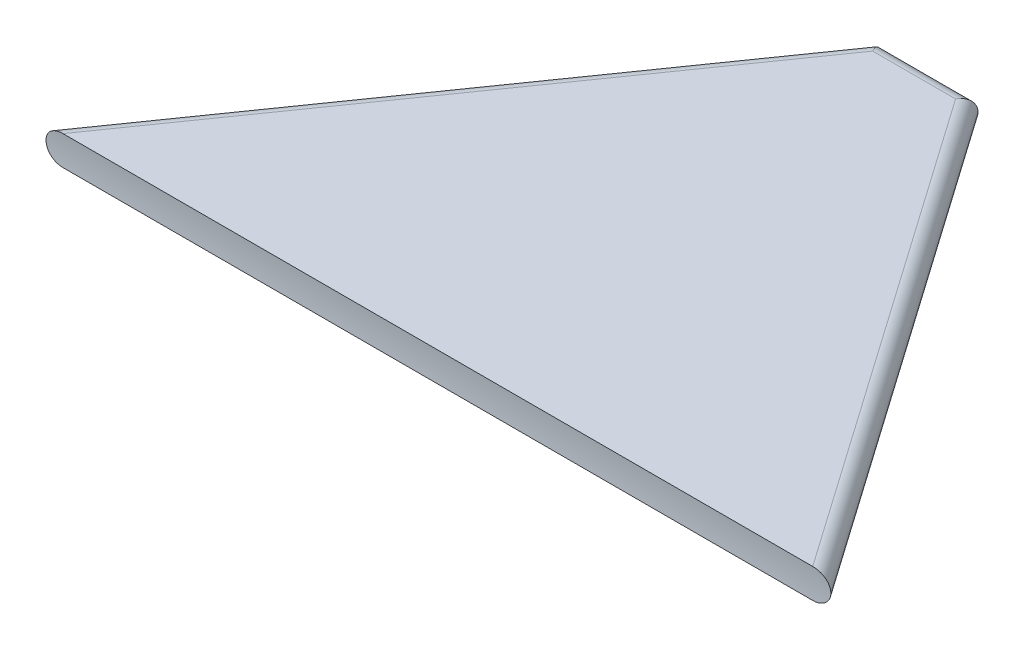
SolidWorks part; units mm, degrees
ref_plane "Спереди" through (0, 0, 0) normal (0, 0, 1) x (1, 0, 0)
ref_plane "Сверху" through (0, 0, 0) normal (0, 1, 0) x (1, 0, 0)
ref_plane "Справа" through (0, 0, 0) normal (1, 0, 0) x (0, 0, -1)
sketch "Эскиз1" plane through (0, 0, 0) normal (0, 1, 0) x (1, 0, 0)
  line L0 (-46.1055, 0) -> (33.8945, 0)
  line L1 (-11.1055, 50) -> (-1.1055, 50)
  line L3 (-11.1055, 50) -> (-46.1055, 0)
  line L4 (-1.1055, 50) -> (33.8945, 0)
  dimension "D1" = 80
  dimension "D2" = 10
  dimension "D3" = 35
  dimension "D4" = 50
extrude "Бобышка-Вытянуть1" add sketch "Эскиз1" along normal blind 3
fillet "Скругление1" radius 1.5 6 edges at (16.3945, 0, -25) (16.3945, 3, -25) (-28.6055, 0, -25) (-28.6055, 3, -25) (-6.1055, 0, -50) (-6.1055, 3, -50)
sketch "Эскиз2" plane through (0, 0, 0) normal (1, 0, 0) x (0, 0, -1)
  line L0 (16.7014, 1.5) -> (-18.9407, 1.5) construction
  line L1 (0, 1.5) -> (50, 1.5) construction
  circle A0 centre (-18.9407, 1.5) radius 19
  dimension "D1" = 38
extrude "Вырез-Вытянуть1" cut sketch "Эскиз2" against normal through all and the other way through all
